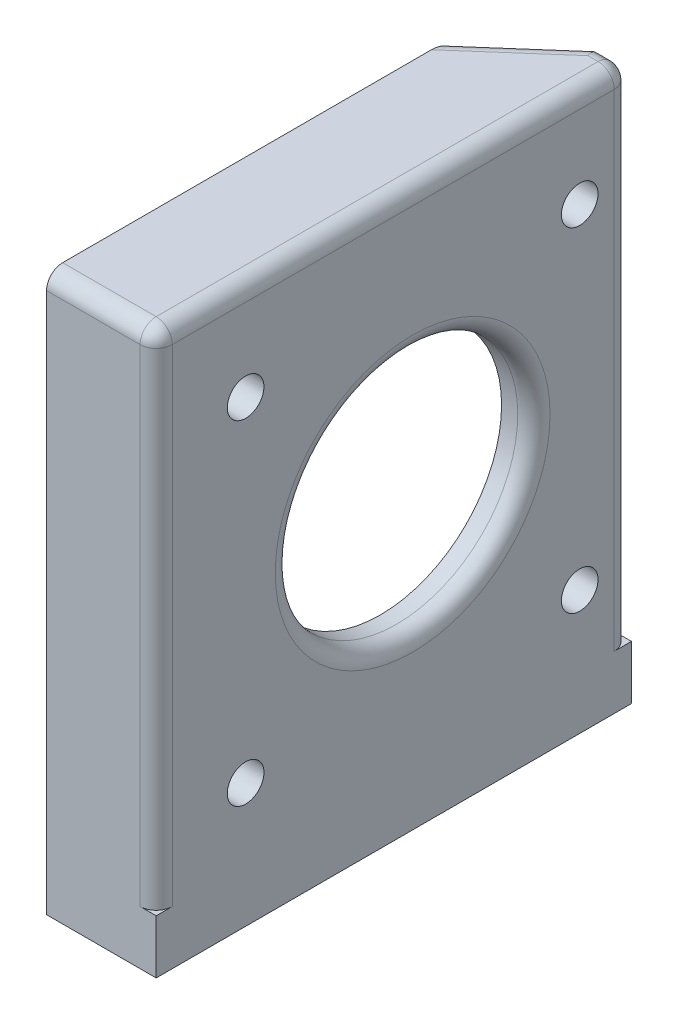
SolidWorks part; units mm, degrees
ref_plane "前基準面" through (0, 0, 0) normal (0, 0, 1) x (1, 0, 0)
ref_plane "上基準面" through (0, 0, 0) normal (0, 1, 0) x (1, 0, 0)
ref_plane "右基準面" through (0, 0, 0) normal (1, 0, 0) x (0, 0, -1)
sketch "草圖1" plane through (0, 0, 0) normal (0, 1, 0) x (1, 0, 0)
  line L0 (-36.2537, 43.5351) -> (203.7463, 43.5351)
  line L1 (203.7463, 43.5351) -> (203.7463, -286.4649)
  line L2 (198.7463, -286.4649) -> (198.7463, -256.4649)
  line L3 (198.7463, -256.4649) -> (183.2463, -256.4649)
  line L4 (183.2463, -256.4649) -> (183.2463, -266.4649)
  line L5 (183.2463, -266.4649) -> (124.7463, -266.4649)
  line L6 (124.7463, -266.4649) -> (124.7463, -262.4649)
  line L7 (124.7463, -262.4649) -> (109.2463, -262.4649)
  line L8 (109.2463, -262.4649) -> (109.2463, -266.4649)
  line L9 (109.2463, -266.4649) -> (-21.2537, -266.4649)
  line L10 (-21.2537, -266.4649) -> (-21.2537, 38.5351)
  line L11 (-21.2537, 38.5351) -> (-36.2537, 38.5351)
  line L12 (-36.2537, 38.5351) -> (-36.2537, 43.5351)
  line L13 (198.7463, -286.4649) -> (203.7463, -286.4649)
  line L15 (203.7463, -286.4649) -> (208.7463, -286.4649)
  line L16 (203.7463, -286.4649) -> (203.7463, -226.4649)
  line L17 (203.7463, -226.4649) -> (208.7463, -226.4649)
  line L18 (208.7463, -286.4649) -> (208.7463, -226.4649)
  line L19 (-36.2537, 43.5351) -> (-6.2537, 43.5351)
  line L20 (-36.2537, 43.5351) -> (-36.2537, 48.5351)
  line L21 (-36.2537, 48.5351) -> (-6.2537, 48.5351)
  line L22 (-6.2537, 43.5351) -> (-6.2537, 48.5351)
  line L23 (203.7463, 43.5351) -> (173.7463, 43.5351)
  line L24 (203.7463, 43.5351) -> (203.7463, 48.5351)
  line L25 (203.7463, 48.5351) -> (173.7463, 48.5351)
  line L26 (173.7463, 43.5351) -> (173.7463, 48.5351)
  line L27 (203.7463, 43.5351) -> (208.7463, 43.5351)
  line L28 (203.7463, 43.5351) -> (203.7463, -16.4649)
  line L29 (203.7463, -16.4649) -> (208.7463, -16.4649)
  line L30 (208.7463, 43.5351) -> (208.7463, -16.4649)
  line L31 (83.7463, 43.5351) -> (98.7463, 43.5351)
  line L32 (83.7463, 43.5351) -> (83.7463, 48.5351)
  line L33 (83.7463, 48.5351) -> (98.7463, 48.5351)
  line L34 (98.7463, 43.5351) -> (98.7463, 48.5351)
  line L35 (83.7463, 43.5351) -> (68.7463, 43.5351)
  line L36 (83.7463, 43.5351) -> (83.7463, 48.5351)
  line L37 (83.7463, 48.5351) -> (68.7463, 48.5351)
  line L38 (68.7463, 43.5351) -> (68.7463, 48.5351)
  line L39 (203.7463, -46.4649) -> (208.7463, -46.4649)
  line L40 (203.7463, -46.4649) -> (203.7463, -106.4649)
  line L41 (203.7463, -106.4649) -> (208.7463, -106.4649)
  line L42 (208.7463, -46.4649) -> (208.7463, -106.4649)
  line L43 (203.7463, -136.4649) -> (208.7463, -136.4649)
  line L44 (203.7463, -136.4649) -> (203.7463, -196.4649)
  line L45 (203.7463, -196.4649) -> (208.7463, -196.4649)
  line L46 (208.7463, -136.4649) -> (208.7463, -196.4649)
  dimension "D3" = 5
  dimension "D1" = 240
  dimension "D2" = 330
  dimension "D4" = 15
  dimension "D5" = 130.5
  dimension "D6" = 4
  dimension "D7" = 4
  dimension "D8" = 15.5
  dimension "D9" = 58.5
  dimension "D10" = 10
  dimension "D11" = 15.5
  dimension "D12" = 30
  dimension "D13" = 5
  dimension "D14" = 60
  dimension "D15" = 5
  dimension "D16" = 5
  dimension "D17" = 30
  dimension "D18" = 5
  dimension "D19" = 30
  dimension "D20" = 60
  dimension "D21" = 5
  dimension "D22" = 5
  dimension "D23" = 15
  dimension "D24" = 5
  dimension "D25" = 15
  dimension "D26" = 60
  dimension "D27" = 5
  dimension "D28" = 30
  dimension "D29" = 60
  dimension "D30" = 5
  dimension "D31" = 30
  dimension "D32" = 30
extrude "填料-伸長1" add sketch "草圖1" along normal blind 5 contours L2 L13 L1 L0 L12 L11 L10 L9 L8 L7 L6 L5 L4 L3 | L15 L18 L17 L1 | L30 L27 L1 L29 | L26 L0 L24 L25 | L0 L22 L21 L20 | L32 L33 L34 L31 | L36 L37 L38 L35 | L46 L45 L44 L43 | L42 L41 L40 L39 region at (-21.2537, 0, -46.0351) region at (91.0303, 0, 111.0679) region at (188.7463, 0, -46.0351) region at (206.2463, 0, -13.5351) region at (206.2463, 0, 256.4649)
fillet "圓角1" radius 5 4 edges at (208.7463, 5, -13.5351) (208.7463, 5, 76.4649) (208.7463, 5, 166.4649) (208.7463, 5, 256.4649)
sketch "草圖2" plane through (0, 5, 0) normal (0, 1, 0) x (1, 0, 0)
  line L1 (-36.2537, 48.5351) -> (208.7463, 48.5351)
  line L2 (-36.2537, 48.5351) -> (-36.2537, -76.4649)
  line L3 (-36.2537, -76.4649) -> (208.7463, -76.4649)
  line L4 (208.7463, 48.5351) -> (208.7463, -76.4649)
  dimension "D1" = 125
extrude "除料-伸長1" cut sketch "草圖2" against normal blind 5
sketch "草圖3" plane through (0, 0, 76.4649) normal (0, 0, -1) x (-1, 0, 0)
  line L1 (21.2537, 0) -> (-88.7463, 0)
  line L2 (21.2537, 0) -> (21.2537, 2.5)
  line L3 (21.2537, 2.5) -> (-88.7463, 2.5)
  line L4 (-88.7463, 0) -> (-88.7463, 2.5)
  line L5 (-93.7463, 2.5) -> (-208.7463, 2.5)
  line L6 (-93.7463, 2.5) -> (-93.7463, 5)
  line L7 (-93.7463, 5) -> (-208.7463, 5)
  line L8 (-208.7463, 2.5) -> (-208.7463, 5)
  point P9 (-93.7463, 3.75)
  dimension "D1" = 2.5
  dimension "D2" = 110
  dimension "D3" = 2.5
  dimension "D4" = 115
  dimension "D5" = 5
extrude "除料-伸長2" cut sketch "草圖3" against normal blind 10
sketch "草圖4" plane through (0, 0, 76.4649) normal (0, 0, -1) x (-1, 0, 0)
  line L1 (-93.7463, 5) -> (-88.7463, 5)
  line L2 (-93.7463, 5) -> (-93.7463, 0)
  line L3 (-93.7463, 0) -> (-88.7463, 0)
  line L4 (-88.7463, 5) -> (-88.7463, 0)
extrude "除料-伸長3" cut sketch "草圖4" against normal blind 5
sketch "草圖5" plane through (0, 0, 266.4649) normal (0, 0, 1) x (1, 0, 0)
  line L0 (109.2463, 5) -> (-21.2537, 5) construction
  line L1 (104.7463, 5) -> (54.7463, 5)
  line L2 (104.7463, 5) -> (104.7463, 51.65)
  line L3 (104.7463, 51.65) -> (54.7463, 51.65)
  line L4 (54.7463, 5) -> (54.7463, 51.65)
  line L5 (124.7463, 5) -> (124.7463, 0) construction
  dimension "D1" = 50
  dimension "D2" = 46.65
  dimension "D3" = 20
  dimension "D4" = 0
extrude "填料-伸長2" add sketch "草圖5" against normal blind 47 contours L2 L1 L4 L3
sketch "草圖6" plane through (54.7463, 0, 0) normal (-1, 0, 0) x (0, 0, 1)
  line L0 (219.4649, 51.65) -> (266.4649, 51.65) construction
  line L1 (222.2649, 49.05) -> (263.6649, 49.05)
  line L2 (222.2649, 49.05) -> (222.2649, 5)
  line L3 (222.2649, 5) -> (263.6649, 5)
  line L4 (263.6649, 49.05) -> (263.6649, 5)
  line L5 (219.4649, 5) -> (219.4649, 51.65) construction
  line L6 (266.4649, 5) -> (266.4649, 51.65) construction
  line L7 (266.4649, 5) -> (76.4649, 5) construction
  dimension "D1" = 2.6
  dimension "D2" = 2.8
  dimension "D3" = 2.8
  dimension "D4" = 0
extrude "除料-伸長4" cut sketch "草圖6" against normal blind 47 contours L2 L1 L4 L3
sketch "草圖7" plane through (101.7463, 0, 0) normal (-1, 0, 0) x (0, 0, 1)
  line L0 (263.6649, 49.05) -> (263.6649, 5) construction
  line L1 (222.2649, 49.05) -> (263.6649, 49.05) construction
  line L2 (222.2649, 49.05) -> (222.2649, 5) construction
  line L5 (263.6649, 49.05) -> (263.6649, 5) construction
  circle A0 centre (242.6649, 27.025) radius 11.25
  dimension "D1" = 41.4
  dimension "D4" = 22.5
  dimension "D2" = 21
  dimension "D3" = 22.025
extrude "除料-伸長5" cut sketch "草圖7" against normal through all
sketch "草圖8" plane through (0, 51.65, 0) normal (0, 1, 0) x (1, 0, 0)
  line L4 (54.7463, -263.6649) -> (101.7463, -222.4649)
  line L8 (104.7463, -219.4649) -> (54.7463, -219.4649) construction
  line L9 (54.7463, -263.6649) -> (54.7463, -219.4649)
  line L13 (104.7463, -219.4649) -> (54.7463, -219.4649)
  line L14 (101.7463, -222.4649) -> (104.7463, -222.4649)
  line L15 (104.7463, -219.4649) -> (104.7463, -266.4649) construction
  line L16 (104.7463, -222.4649) -> (104.7463, -219.4649)
  dimension "D2" = 3
extrude "除料-伸長6" cut sketch "草圖8" against normal blind 46.65
sketch "草圖10" plane through (101.7463, 0, 0) normal (-1, 0, 0) x (0, 0, 1)
  circle A0 centre (227.1649, 42.525) radius 1.7
  circle A1 centre (258.1649, 42.525) radius 1.7
  circle A2 centre (258.1649, 11.525) radius 1.7
  circle A3 centre (227.1649, 11.525) radius 1.7
  circle A4 centre (242.6649, 27.025) radius 11.25 construction
  dimension "D1" = 3.4
  dimension "D2" = 3.4
  dimension "D3" = 3.4
  dimension "D4" = 3.4
  dimension "D5" = 15.5
  dimension "D6" = 15.5
  dimension "D7" = 15.5
  dimension "D8" = 15.5
  dimension "D9" = 15.5
  dimension "D10" = 15.5
  dimension "D11" = 15.5
  dimension "D12" = 15.5
extrude "除料-伸長7" cut sketch "草圖10" against normal through all
sketch "草圖13" plane through (104.7463, 0, 0) normal (1, 0, 0) x (0, 0, -1)
  circle A0 centre (-242.6649, 27.025) radius 25
  dimension "D1" = 50
extrude "除料-伸長9" cut sketch "草圖13" along normal blind 20
fillet "圓角11" radius 1.497 9 edges at (104.7463, 51.65, 244.4649) (79.7463, 51.65, 266.4649) (54.7463, 51.65, 265.0649) (78.2463, 51.65, 243.0649) (103.2463, 51.65, 222.4649) (54.7463, 28.325, 266.4649) (104.7463, 28.325, 266.4649) (104.7463, 27.025, 231.4149) (104.7463, 28.325, 222.4649)
sketch "草圖17" plane through (0, 51.65, 0) normal (0, 1, 0) x (1, 0, 0)
  line L0 (103.2493, -266.4649) -> (56.2433, -266.4649) construction
  line L1 (94.5719, -266.4649) -> (104.7463, -266.4649)
  line L2 (94.5719, -266.4649) -> (94.5719, -222.3607)
  line L3 (94.5719, -222.3607) -> (104.7463, -222.3607)
  line L4 (104.7463, -266.4649) -> (104.7463, -222.3607)
extrude "除料-伸長11" cut sketch "草圖17" against normal through all flip side to cut
equation "\"1.5.0000mm\"=10"
